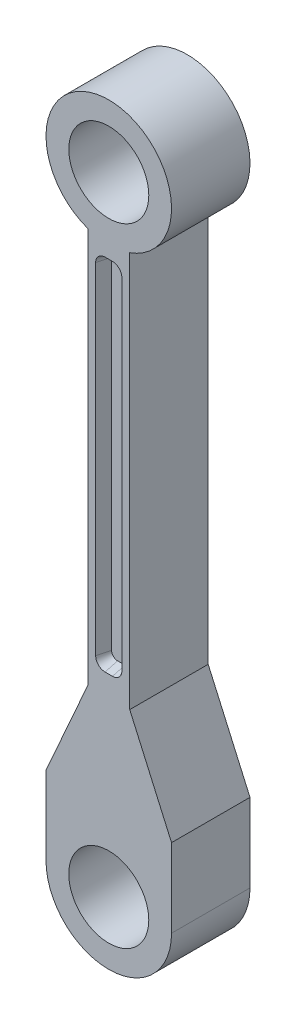
SolidWorks part; units mm, degrees
ref_plane "Front" through (0, 0, 0) normal (0, 0, 1) x (1, 0, 0)
ref_plane "Top" through (0, 0, 0) normal (0, 1, 0) x (1, 0, 0)
ref_plane "Right" through (0, 0, 0) normal (1, 0, 0) x (0, 0, -1)
sketch "Sketch2" plane through (0, 0, 0) normal (0, 0, 1) x (1, 0, 0)
  line L0 (0, 27.9448) -> (0, -117.3817) construction
  line L1 (-50.0232, 11.0248) -> (63.6732, 11.0248) construction
  line L2 (-50.0232, -1.1672) -> (63.6732, -1.1672) construction
  line L3 (-50.0232, -90.5752) -> (95.9384, -90.5752) construction
  line L4 (-50.0232, -77.8752) -> (95.9384, -77.8752) construction
  line L5 (10.16, -90.5752) -> (10.16, -77.8752)
  line L6 (-10.16, -90.5752) -> (-10.16, -77.8752)
  line L7 (10.16, -77.8752) -> (3.3942, -62.6072)
  line L8 (-10.16, -77.8752) -> (-3.3942, -62.6072)
  line L9 (3.3942, -62.6072) -> (3.3942, 1.4485)
  line L10 (-3.3942, -62.6072) -> (-3.3942, 1.4485)
  line L11 (-31.7845, -59.3332) -> (48.39, -59.3332) construction
  arc A0 (3.3942, 1.4485) -> (-3.3942, 1.4485) centre (0, 11.0248) ccw
  circle A1 centre (0, 11.0248) radius 6.477
  arc A2 (-10.16, -90.5752) -> (10.16, -90.5752) centre (0, -90.5752) ccw
  circle A3 centre (0, -90.5752) radius 6.477
  point P32 (-2.1242, -1.1672)
  point P35 (2.1242, -1.1672)
  point P38 (-2.1242, -59.3332)
  point P41 (2.1242, -59.3332)
  dimension "D1" = 12.954
  dimension "D2" = 20.32
  dimension "D5" = 12.954
  dimension "D3" = 12.192
  dimension "D4" = 12.7
  dimension "D6" = 31.242
  dimension "D7" = 1.27
extrude "Boss-Extrude5" add sketch "Sketch2" along normal blind 6.35 and the other way blind 6.35
sketch "Sketch3" plane through (0, 0, 6.35) normal (0, 0, 1) x (1, 0, 0)
  line L0 (0, -90.5752) -> (-55.2141, -90.5752) construction
  line L1 (0, -59.3332) -> (-67.1401, -59.3332) construction
  line L2 (0, 11.0248) -> (53.0106, 11.0248) construction
  line L3 (53.0106, -1.1672) -> (-59.9237, -1.1672) construction
  line L4 (2.1242, -2.6912) -> (2.1242, -57.8092)
  line L5 (0, 24.0932) -> (0, -116.5626) construction
  line L6 (-2.1242, -2.6912) -> (-2.1242, -57.8092)
  line L7 (0.6002, -59.3332) -> (-0.6002, -59.3332)
  line L8 (0.6002, -1.1672) -> (-0.6002, -1.1672)
  line L9 (0.6002, -1.6752) -> (-0.6002, -1.6752)
  line L10 (1.6162, -2.6912) -> (1.6162, -57.8092)
  line L11 (0.6002, -58.8252) -> (-0.6002, -58.8252)
  line L12 (-1.6162, -2.6912) -> (-1.6162, -57.8092)
  arc A0 (-0.6002, -59.3332) -> (-2.1242, -57.8092) centre (-0.6002, -57.8092) cw
  arc A1 (2.1242, -57.8092) -> (0.6002, -59.3332) centre (0.6002, -57.8092) cw
  arc A2 (2.1242, -2.6912) -> (0.6002, -1.1672) centre (0.6002, -2.6912) ccw
  arc A3 (-2.1242, -2.6912) -> (-0.6002, -1.1672) centre (-0.6002, -2.6912) cw
  arc A4 (-1.6162, -2.6912) -> (-0.6002, -1.6752) centre (-0.6002, -2.6912) cw
  arc A5 (1.6162, -2.6912) -> (0.6002, -1.6752) centre (0.6002, -2.6912) ccw
  arc A6 (1.6162, -57.8092) -> (0.6002, -58.8252) centre (0.6002, -57.8092) cw
  arc A7 (-0.6002, -58.8252) -> (-1.6162, -57.8092) centre (-0.6002, -57.8092) cw
  point P15 (-2.1242, -59.3332)
  point P25 (2.1242, -1.1672)
  point P28 (-2.1242, -1.1672)
  dimension "D3" = 1.524
  dimension "D1" = 31.242
  dimension "D2" = 12.192
  dimension "D4" = 0.508
extrude "Cut-Extrude1" cut sketch "Sketch3" against normal blind 2.032 draft 15 contours A7 L11 A6 L10 A5 L9 A4 L12 | A3 L6 A0 L7 A1 L4 A2 L8 L11 A7 L12 A4 L9 A5 L10 A6 region at (2.0658, -30.2502, 6.35) region at (0, -30.2502, 6.35)
ref_plane "Plane1" through (0, 0, 0) normal (0, 0, 1) x (1, 0, 0)
mirror "Mirror1" about plane through (0, 0, 0) normal (0, 0, 1) of "Cut-Extrude1"
